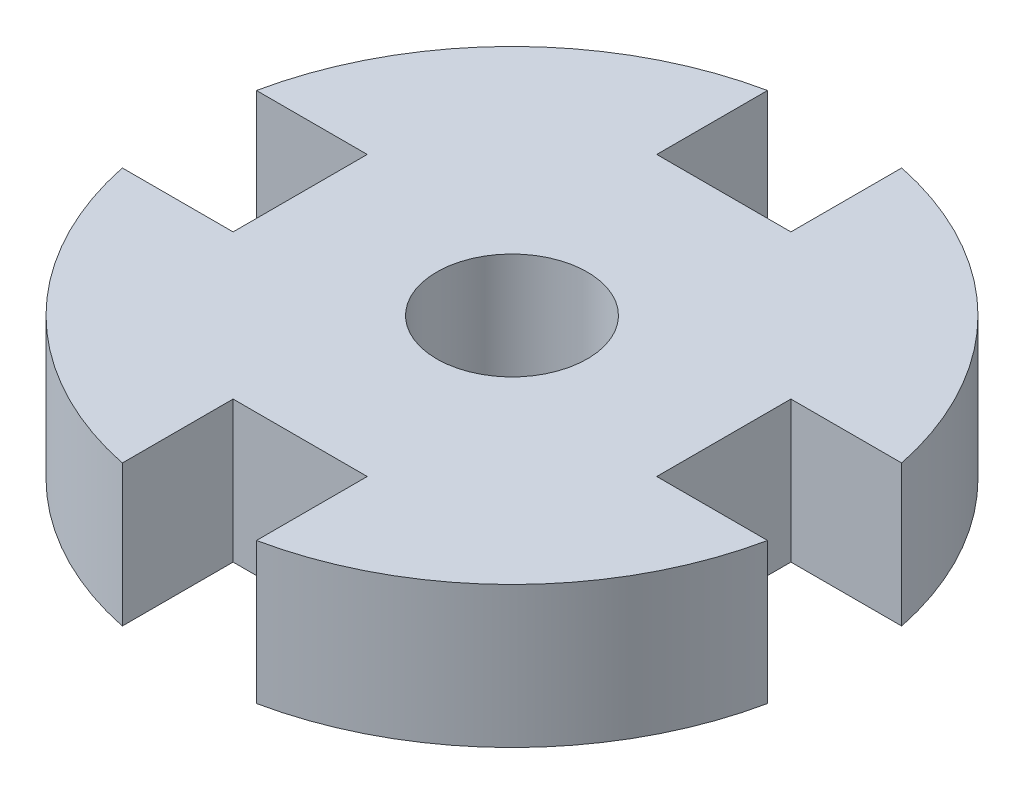
SolidWorks part; units mm, degrees
ref_plane "Front Plane" through (0, 0, 0) normal (0, 0, 1) x (1, 0, 0)
ref_plane "Top Plane" through (0, 0, 0) normal (0, 1, 0) x (1, 0, 0)
ref_plane "Right Plane" through (0, 0, 0) normal (1, 0, 0) x (0, 0, -1)
sketch "Sketch1" plane through (0, 0, 0) normal (0, 1, 0) x (1, 0, 0)
  circle A0 centre (0, 0) radius 1.6
  circle A2 centre (0, 0) radius 7
  dimension "D1" = 3.2
  dimension "D2" = 14
extrude "Boss-Extrude1" add sketch "Sketch1" along normal blind 1.5 and the other way blind 1.5
sketch "Sketch2" plane through (0, 1.5, 0) normal (0, 1, 0) x (1, 0, 0)
  line L1 (9.5, -1.425) -> (4.5, -1.425)
  line L2 (9.5, -1.425) -> (9.5, 1.425)
  line L3 (9.5, 1.425) -> (4.5, 1.425)
  line L4 (4.5, -1.425) -> (4.5, 1.425)
  line L5 (7, 1.425) -> (7, -1.425) construction
  line L6 (9.5, 0) -> (4.5, 0) construction
  circle A0 centre (0, 0) radius 7 construction
  point P0 (7, 0)
  dimension "D1" = 2.85
  dimension "D2" = 2.5
extrude "Cut-Extrude1" cut sketch "Sketch2" against normal through all
pattern_circular "CirPattern1" count 4 over 360 about axis through (0, -1.5, 0) along (0, 1, 0) of "Cut-Extrude1" reverse direction yes
